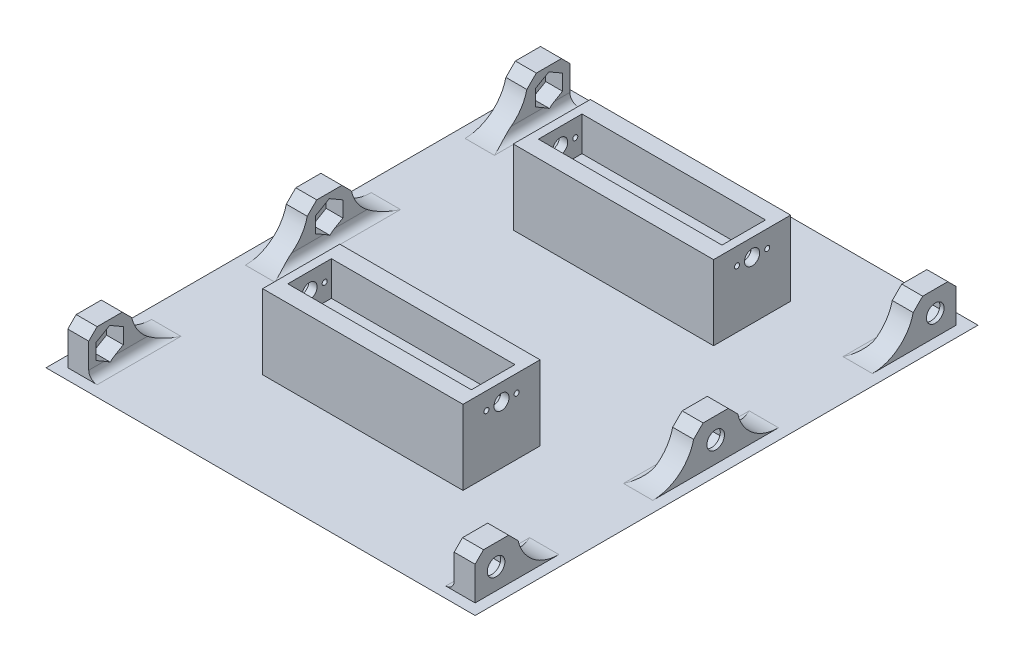
SolidWorks part; units mm, degrees
ref_plane "Front Plane" through (0, 0, 0) normal (0, 0, 1) x (1, 0, 0)
ref_plane "Top Plane" through (0, 0, 0) normal (0, 1, 0) x (1, 0, 0)
ref_plane "Right Plane" through (0, 0, 0) normal (1, 0, 0) x (0, 0, -1)
sketch "Sketch1" plane through (0, 0, 0) normal (0, 1, 0) x (1, 0, 0)
  line L1 (65.024, 76.2) -> (-65.024, 76.2)
  line L2 (65.024, 76.2) -> (65.024, -76.2)
  line L3 (65.024, -76.2) -> (-65.024, -76.2)
  line L4 (-65.024, 76.2) -> (-65.024, -76.2)
  line L5 (65.024, 76.2) -> (-65.024, -76.2) construction
  line L6 (65.024, -76.2) -> (-65.024, 76.2) construction
  point P0 (0, 0)
  dimension "D1" = 130.048
  dimension "D2" = 152.4
extrude "Boss-Extrude1" add sketch "Sketch1" along normal blind 2.54 contours L1 L4 L3 L2
chamfer "Chamfer1" distance 2.54 angle 45 4 edges at (0, 0, -76.2) (-65.024, 0, 0) (0, 0, 76.2) (65.024, 0, 0)
sketch "Sketch2" plane through (0, 2.54, 0) normal (0, 1, 0) x (1, 0, 0)
  line L1 (-27.813, 49.022) -> (27.813, 49.022)
  line L2 (-27.813, 49.022) -> (-27.813, 35.814)
  line L3 (-27.813, 35.814) -> (27.813, 35.814)
  line L4 (27.813, 49.022) -> (27.813, 35.814)
  line L5 (-27.813, 49.022) -> (27.813, 35.814) construction
  line L6 (-27.813, 35.814) -> (27.813, 49.022) construction
  line L7 (-27.813, -26.924) -> (27.813, -26.924)
  line L8 (-27.813, -26.924) -> (-27.813, -40.132)
  line L9 (-27.813, -40.132) -> (27.813, -40.132)
  line L10 (27.813, -26.924) -> (27.813, -40.132)
  line L11 (-27.813, -26.924) -> (27.813, -40.132) construction
  line L12 (-27.813, -40.132) -> (27.813, -26.924) construction
  line L13 (30.353, 54.102) -> (-30.353, 54.102)
  line L14 (30.353, 54.102) -> (30.353, 30.734)
  line L15 (30.353, 30.734) -> (-30.353, 30.734)
  line L16 (-30.353, 54.102) -> (-30.353, 30.734)
  line L17 (30.353, 54.102) -> (-30.353, 30.734) construction
  line L18 (30.353, 30.734) -> (-30.353, 54.102) construction
  line L19 (30.353, -45.212) -> (-30.353, -45.212)
  line L20 (30.353, -45.212) -> (30.353, -21.844)
  line L21 (30.353, -21.844) -> (-30.353, -21.844)
  line L22 (-30.353, -45.212) -> (-30.353, -21.844)
  line L23 (30.353, -45.212) -> (-30.353, -21.844) construction
  line L24 (30.353, -21.844) -> (-30.353, -45.212) construction
  point P0 (0, 42.418)
  point P5 (0, -33.528)
  point P10 (0, 42.418)
  point P16 (0, -33.528)
  dimension "D1" = 55.626
  dimension "D2" = 13.208
  dimension "D3" = 42.418
  dimension "D4" = 33.528
  dimension "D5" = 2.54
  dimension "D6" = 5.08
extrude "Boss-Extrude2" add sketch "Sketch2" along normal blind 22.606
extrude "Boss-Extrude3" add sketch "Sketch2<2>" along normal blind 12.192 contours L10 L7 L8 L9 | L4 L1 L2 L3 region at (0, 2.54, -42.418) region at (0, 2.54, 33.528)
sketch "Sketch2<2>" plane through (0, 2.54, 0) normal (0, 1, 0) x (1, 0, 0) same geometry as "Sketch2"
sketch "Sketch3" plane through (0, 0, 0) normal (1, 0, 0) x (0, 0, -1)
  line L0 (42.418, 25.146) -> (42.418, 14.732) construction
  line L1 (30.734, 25.146) -> (54.102, 25.146) construction
  line L2 (49.022, 14.732) -> (35.814, 14.732) construction
  line L3 (37.846, 19.939) -> (46.99, 19.939) construction
  line L4 (-21.844, 25.146) -> (30.734, 25.146) construction
  line L5 (4.445, 25.146) -> (4.445, 2.54) construction
  line L6 (76.2, 2.54) -> (-76.2, 2.54) construction
  line L7 (-28.956, 19.939) -> (-38.1, 19.939) construction
  line L8 (-33.528, 25.146) -> (-33.528, 14.732) construction
  circle A0 centre (42.418, 19.939) radius 2.286
  circle A1 centre (46.99, 19.939) radius 0.762
  circle A2 centre (37.846, 19.939) radius 0.762
  circle A3 centre (-28.956, 19.939) radius 0.762
  circle A4 centre (-38.1, 19.939) radius 0.762
  circle A5 centre (-33.528, 19.939) radius 2.286
  point P8 (42.418, 19.939)
  dimension "D1" = 1.524
  dimension "D2" = 4.572
  dimension "D3" = 7.62
extrude "Cut-Extrude1" cut sketch "Sketch3" against normal through all both and the other way through all
sketch "Sketch4" plane through (0, 2.54, 0) normal (0, 1, 0) x (1, 0, 0)
  line L0 (0, 76.2) -> (0, -76.2) construction
  line L1 (-61.722, 72.898) -> (-55.372, 72.898)
  line L2 (-61.722, 72.898) -> (-61.722, 60.198)
  line L3 (-61.722, 60.198) -> (-55.372, 60.198)
  line L4 (-55.372, 72.898) -> (-55.372, 60.198)
  line L5 (-61.722, 72.898) -> (-55.372, 60.198) construction
  line L6 (-61.722, 60.198) -> (-55.372, 72.898) construction
  line L7 (-61.722, 6.35) -> (-55.372, 6.35)
  line L8 (-61.722, 6.35) -> (-61.722, -6.35)
  line L9 (-61.722, -6.35) -> (-55.372, -6.35)
  line L10 (-55.372, 6.35) -> (-55.372, -6.35)
  line L11 (-61.722, 6.35) -> (-55.372, -6.35) construction
  line L12 (-61.722, -6.35) -> (-55.372, 6.35) construction
  line L13 (-61.722, -60.198) -> (-55.372, -60.198)
  line L14 (-61.722, -60.198) -> (-61.722, -72.898)
  line L15 (-61.722, -72.898) -> (-55.372, -72.898)
  line L16 (-55.372, -60.198) -> (-55.372, -72.898)
  line L17 (-61.722, -60.198) -> (-55.372, -72.898) construction
  line L18 (-61.722, -72.898) -> (-55.372, -60.198) construction
  line L19 (65.024, 76.2) -> (-65.024, 76.2) construction
  line L20 (65.024, -76.2) -> (-65.024, -76.2) construction
  line L21 (-65.024, 76.2) -> (-65.024, -76.2) construction
  line L22 (61.722, -72.898) -> (55.372, -60.198) construction
  line L23 (61.722, -60.198) -> (55.372, -72.898) construction
  line L24 (61.722, -6.35) -> (55.372, 6.35) construction
  line L25 (61.722, 6.35) -> (55.372, -6.35) construction
  line L26 (61.722, 60.198) -> (55.372, 72.898) construction
  line L27 (61.722, 72.898) -> (55.372, 60.198) construction
  line L28 (55.372, -60.198) -> (55.372, -72.898)
  line L29 (61.722, -72.898) -> (55.372, -72.898)
  line L30 (61.722, -60.198) -> (61.722, -72.898)
  line L31 (61.722, -60.198) -> (55.372, -60.198)
  line L32 (55.372, 6.35) -> (55.372, -6.35)
  line L33 (61.722, -6.35) -> (55.372, -6.35)
  line L34 (61.722, 6.35) -> (61.722, -6.35)
  line L35 (61.722, 6.35) -> (55.372, 6.35)
  line L36 (55.372, 72.898) -> (55.372, 60.198)
  line L37 (61.722, 60.198) -> (55.372, 60.198)
  line L38 (61.722, 72.898) -> (61.722, 60.198)
  line L39 (61.722, 72.898) -> (55.372, 72.898)
  point P4 (-58.547, 66.548)
  point P9 (-58.547, 0)
  point P14 (-58.547, -66.548)
  point P23 (-58.547, 72.898)
  point P24 (0, 0)
  point P38 (58.547, -66.548)
  point P39 (58.547, 0)
  point P40 (58.547, 66.548)
  dimension "D1" = 12.7
  dimension "D2" = 6.35
  dimension "D3" = 3.302
  dimension "D4" = 3.302
  dimension "D5" = 3.302
extrude "Boss-Extrude4" add sketch "Sketch4" along normal blind 12.7
sketch "Sketch5" plane through (0, 0, 0) normal (1, 0, 0) x (0, 0, -1)
  line L0 (0, 15.24) -> (0, 2.54) construction
  line L1 (-6.35, 15.24) -> (6.35, 15.24) construction
  line L2 (76.2, 2.54) -> (-76.2, 2.54) construction
  line L3 (66.548, 15.24) -> (66.548, 2.54) construction
  line L4 (0, 4.124) -> (4.1275, 6.507)
  line L5 (4.1275, 6.507) -> (4.1275, 11.273)
  line L6 (4.1275, 11.273) -> (0, 13.656)
  line L7 (0, 13.656) -> (-4.1275, 11.273)
  line L8 (-4.1275, 11.273) -> (-4.1275, 6.507)
  line L9 (-4.1275, 6.507) -> (0, 4.124)
  line L10 (60.198, 15.24) -> (72.898, 15.24) construction
  line L11 (60.198, 2.54) -> (72.898, 2.54) construction
  line L12 (-66.548, 15.24) -> (-66.548, 2.54) construction
  line L13 (-72.898, 15.24) -> (-60.198, 15.24) construction
  line L14 (-72.898, 2.54) -> (-60.198, 2.54) construction
  line L16 (-66.548, 4.124) -> (-62.4205, 6.507)
  line L17 (-62.4205, 6.507) -> (-62.4205, 11.273)
  line L18 (-62.4205, 11.273) -> (-66.548, 13.656)
  line L19 (-66.548, 13.656) -> (-70.6755, 11.273)
  line L20 (-70.6755, 11.273) -> (-70.6755, 6.507)
  line L21 (-70.6755, 6.507) -> (-66.548, 4.124)
  line L22 (66.548, 4.124) -> (70.6755, 6.507)
  line L23 (70.6755, 6.507) -> (70.6755, 11.273)
  line L24 (70.6755, 11.273) -> (66.548, 13.656)
  line L25 (66.548, 13.656) -> (62.4205, 11.273)
  line L26 (62.4205, 11.273) -> (62.4205, 6.507)
  line L27 (62.4205, 6.507) -> (66.548, 4.124)
  circle A0 centre (0, 8.89) radius 4.1275 construction
  circle A1 centre (0, 8.89) radius 2.667
  circle A2 centre (-66.548, 8.89) radius 4.1275 construction
  circle A3 centre (66.548, 8.89) radius 4.1275 construction
  circle A4 centre (-66.548, 8.89) radius 2.667
  circle A5 centre (66.548, 8.89) radius 2.667
  point P7 (-2.0637, 5.3155)
  dimension "D2" = 5.334
  dimension "D1" = 8.255
extrude "Cut-Extrude2" cut sketch "Sketch5" against normal through all both and the other way through all contours A4 | A1 | A5 region at (0, 8.89, 0) region at (0, 8.89, 66.548) region at (0, 8.89, -66.548)
extrude "Cut-Extrude3" cut sketch "Sketch5<3>" against normal offset from surface 1.27 and the other way offset from surface 1.27 up to face at (-61.722, 8.89, 63.881) other way up to face at (61.722, 8.89, 69.215)
sketch "Sketch5<3>" plane through (0, 0, 0) normal (1, 0, 0) x (0, 0, -1) same geometry as "Sketch5"
fillet "Fillet1" radius 12.7 8 edges at (58.547, 2.54, 60.198) (58.547, 2.54, 6.35) (58.547, 2.54, -6.35) (58.547, 2.54, -60.198) (-58.547, 2.54, 60.198) (-58.547, 2.54, 6.35) (-58.547, 2.54, -6.35) (-58.547, 2.54, -60.198)
fillet "Fillet2" radius 2.54 6 edges at (55.372, 2.54, 60.198) (-55.372, 2.54, 60.198) (-55.372, 2.54, 0) (55.372, 2.54, 0) (55.372, 2.54, -60.198) (-55.372, 2.54, -60.198)
chamfer "Chamfer2" distance 2.54 angle 45 12 edges at (58.547, 15.24, -72.898) (-58.547, 15.24, -72.898) (-58.547, 15.24, 72.898) (58.547, 15.24, 60.198) (58.547, 15.24, 72.898) (58.547, 15.24, 6.35) (58.547, 15.24, -6.35) (58.547, 15.24, -60.198) (-58.547, 15.24, -60.198) (-58.547, 15.24, -6.35) (-58.547, 15.24, 6.35) (-58.547, 15.24, 60.198)
